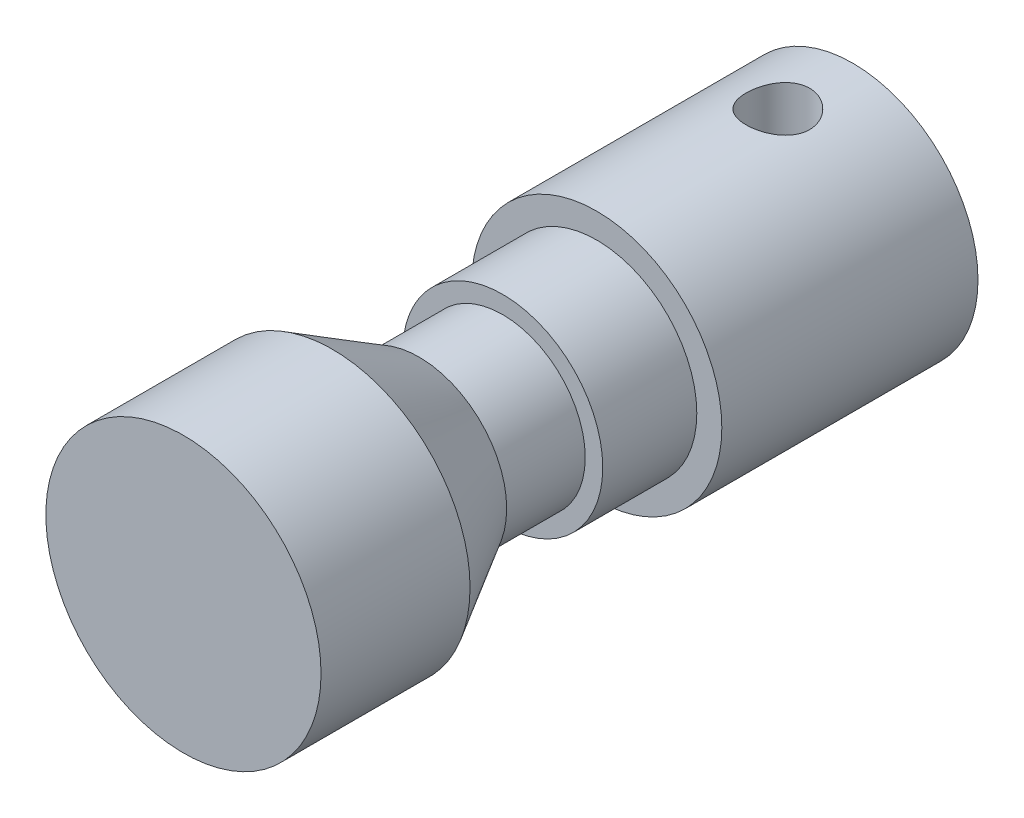
SolidWorks part; units mm, degrees
ref_plane "Plan de face" through (0, 0, 0) normal (0, 0, 1) x (1, 0, 0)
ref_plane "Plan de dessus" through (0, 0, 0) normal (0, 1, 0) x (1, 0, 0)
ref_plane "Plan de droite" through (0, 0, 0) normal (1, 0, 0) x (0, 0, -1)
sketch "Esquisse1" plane through (0, 0, 0) normal (0, 0, 1) x (1, 0, 0)
  circle A0 centre (0, 0) radius 25
extrude "Boss.-Extru.1" add sketch "Esquisse1" along normal blind 51.2
sketch "Esquisse2" plane through (0, 0, 51.2) normal (0, 0, 1) x (1, 0, 0)
  circle A0 centre (0, 0) radius 20
extrude "Boss.-Extru.2" add sketch "Esquisse2" along normal blind 18.8
sketch "Esquisse3" plane through (0, 0, 70) normal (0, 0, 1) x (1, 0, 0)
  circle A0 centre (0, 0) radius 16.5
extrude "Boss.-Extru.3" add sketch "Esquisse3" along normal blind 16.7
sketch "Esquisse4" plane through (0, 0, 86.7) normal (0, 0, 1) x (1, 0, 0)
  circle A0 centre (0, 0) radius 27.5
extrude "Boss.-Extru.4" add sketch "Esquisse4" along normal blind 47.1
chamfer "Chanfrein1" distance 10 angle 60 1 edges at (27.5, 0, 86.7) first distance on face at (16.5, 0, 86.7)
sketch "Esquisse12" plane through (0, 0, 0) normal (0, 1, 0) x (1, 0, 0)
  line L0 (0, -30.25) -> (0, 30.25) construction
  line L1 (-30.25, 0) -> (30.25, 0) construction
  circle A0 centre (0, -15) radius 6.35
  point P0 (0, -15)
  dimension "D1" = 15
extrude "Enlèv. mat.-Extru.1" cut sketch "Esquisse12" against normal through all both and the other way through all
